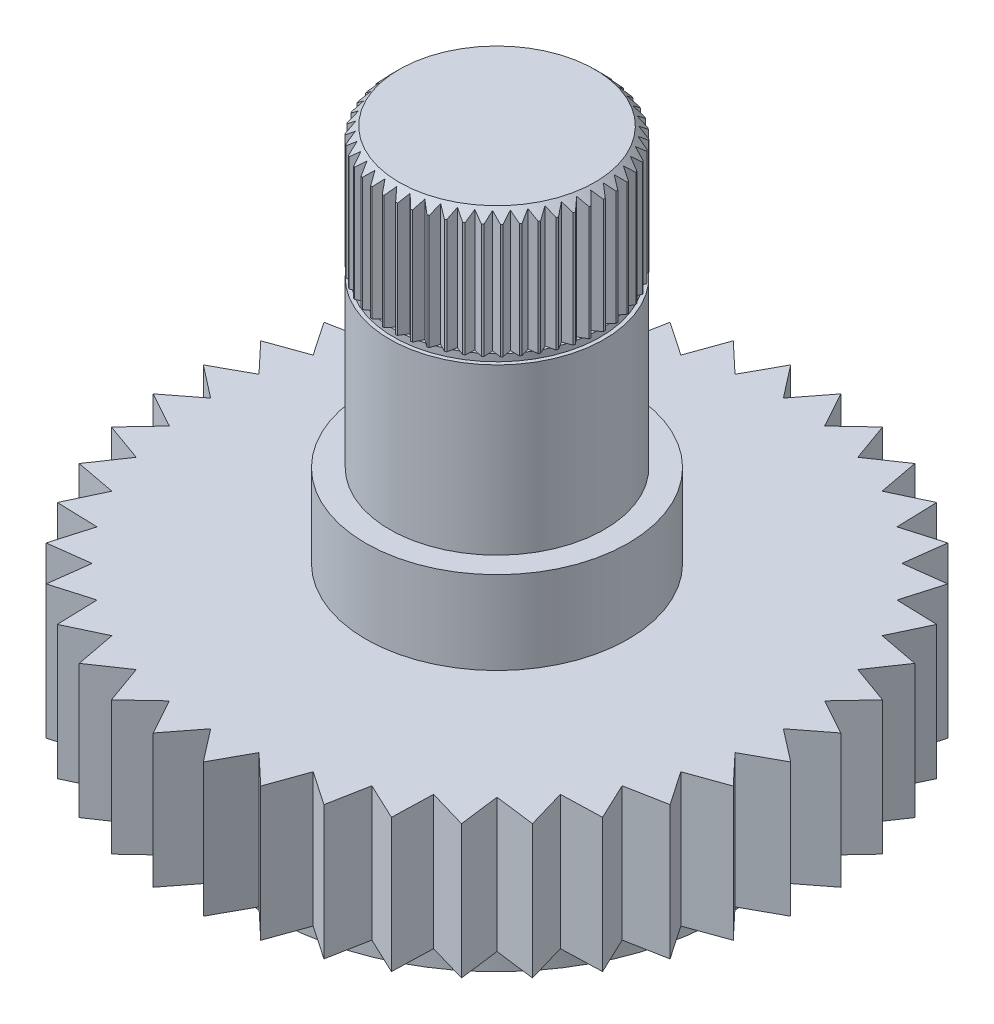
SolidWorks part; units mm, degrees
material "Chrome Stainless Steel"
ref_plane "Front Plane" through (0, 0, 0) normal (0, 0, 1) x (1, 0, 0)
ref_plane "Top Plane" through (0, 0, 0) normal (0, 1, 0) x (1, 0, 0)
ref_plane "Right Plane" through (0, 0, 0) normal (1, 0, 0) x (0, 0, -1)
sketch "Sketch1" plane through (0, 0, 0) normal (0, 0, 1) x (1, 0, 0)
  line L0 (0, 0) -> (0, 35.5657) construction
  line L1 (6.016, 0) -> (8.509, 0)
  line L2 (8.509, 0) -> (8.509, 3.556)
  line L3 (8.509, 3.556) -> (3.4925, 3.556)
  line L4 (2.8575, 5.7658) -> (2.8575, 10.1501)
  line L5 (2.8575, 13.6398) -> (0, 13.6398)
  line L6 (0, 13.6398) -> (0, 0.9398)
  line L7 (0, 0.9398) -> (5, 0.9398)
  line L8 (5, 0.9398) -> (5, -1.6002)
  line L9 (2.8575, 10.3378) -> (2.7555, 10.3378)
  line L10 (2.7555, 10.3378) -> (2.7555, 10.1501)
  line L11 (2.7555, 10.1501) -> (2.8575, 10.1501)
  line L12 (2.8575, 10.3378) -> (2.8575, 13.6398)
  line L13 (2.8575, 5.7658) -> (3.4925, 5.7658)
  line L14 (3.4925, 5.7658) -> (3.4925, 3.556)
  line L15 (6.016, 0) -> (6.016, -1.6002)
  line L16 (6.016, -1.6002) -> (5, -1.6002)
  dimension "D1" = 5.715
  dimension "D2" = 10
  dimension "D3" = 17.018
  dimension "D4" = 3.556
  dimension "D5" = 15.24
  dimension "D6" = 2.54
  dimension "D7" = 7.366
  dimension "D8" = 6.985
  dimension "D9" = 1.6002
  dimension "D10" = 1.016
  dimension "D11" = 3.302
revolve "Revolve1" add sketch "Sketch1" angle 360 about L0
sketch "Sketch2" plane through (0, 0.9398, 0) normal (0, -1, 0) x (1, 0, 0)
  line L0 (0, 1.5875) -> (0, -1.5875)
  arc A0 (0, 1.5875) -> (0, -1.5875) centre (0, 0) cw
  dimension "D1" = 1.5875
extrude "Cut-Extrude1" cut sketch "Sketch2" against normal blind 2.032
sketch "Sketch3" plane through (0, 3.556, 0) normal (0, 1, 0) x (-1, 0, 0)
  line L0 (0.6676, -8.4828) -> (0, -7.62)
  line L1 (0, -7.62) -> (-0.6676, -8.4828)
  line L2 (-0.6676, -8.4828) -> (-1.192, -7.5262) construction
  line L3 (-1.192, -7.5262) -> (0, 0) construction
  line L4 (0, 0) -> (-0.6676, -8.4828) construction
  line L5 (0, -7.62) -> (0, 0) construction
  circle A0 centre (0, 0) radius 8.509 construction
  arc A1 (-0.6676, -8.4828) -> (0.6676, -8.4828) centre (0, 0) ccw
  circle A2 centre (0, 0) radius 7.62 construction
  dimension "D1" = 9
extrude "Cut-Extrude2" cut sketch "Sketch3" against normal through all
pattern_circular "CirPattern1" count 40 over 360 about axis through (0, 0, 0) along (0, 1, 0) of "Cut-Extrude2"
chamfer "Chamfer1" distance 0.254 angle 45 1 edges at (0, 13.6398, -2.8575)
sketch "Sketch4" plane through (0, 13.6398, 0) normal (0, 1, 0) x (-1, 0, 0)
  line L0 (0.1555, -2.8533) -> (0, -2.667)
  line L1 (0, -2.667) -> (-0.1555, -2.8533)
  line L2 (-0.1555, -2.8533) -> (-0.2898, -2.6512) construction
  line L3 (-0.2898, -2.6512) -> (0, 0) construction
  line L4 (0, 0) -> (-0.1555, -2.8533) construction
  line L5 (0, -2.667) -> (0, 0) construction
  circle A0 centre (0, 0) radius 2.8575 construction
  circle A1 centre (0, 0) radius 2.667 construction
  arc A2 (-0.1555, -2.8533) -> (0.1555, -2.8533) centre (0, 0) ccw
  dimension "D2" = 5.334
  dimension "D1" = 6.238
extrude "Cut-Extrude3" cut sketch "Sketch4" against normal up to surface (3.302 mm away) up to face at (0, 10.3378, -2.8575)
pattern_circular "CirPattern2" count 50 over 360 about axis through (0, 0, 0) along (0, 1, 0) of "Cut-Extrude3"
ref_axis "Axis1" through (0, -31.0516, 0) along (0, 1, 0)
equation "\"D1@Sketch3\"=360/\"D1@CirPattern1\""
